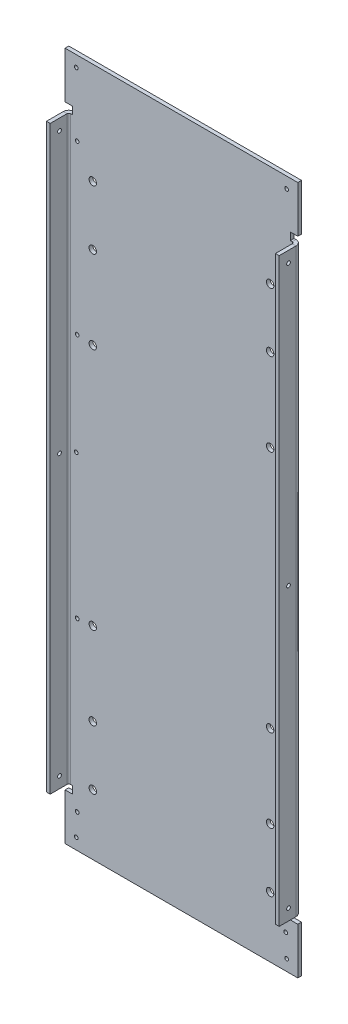
SolidWorks part; units mm, degrees
note: The reader was unsure of these and kept them because the rebuilt part matched: flange length of "Edge-Flange1".
ref_plane "Front Plane" through (0, 0, 0) normal (1, 0, 0) x (0, 1, 0)
ref_plane "Top Plane" through (0, 0, 0) normal (0, 0, 1) x (0, 1, 0)
ref_plane "Right Plane" through (0, 0, 0) normal (0, 1, 0) x (-1, 0, 0)
sketch "Sketch1" plane through (0, 0, 0) normal (0, 0, 1) x (0, 1, 0)
  line L0 (-76.28, 47.625) -> (-76.28, -47.625) construction
  line L1 (185, 62.5) -> (160, 62.5)
  line L2 (185, 62.5) -> (185, -62.5)
  line L3 (185, -62.5) -> (160, -62.5)
  line L4 (-185, 62.5) -> (-185, -62.5)
  line L5 (185, 62.5) -> (-185, -62.5) construction
  line L6 (185, -62.5) -> (-185, 62.5) construction
  line L7 (-11, 62.5) -> (-11, -62.5) construction
  line L8 (-182, 50.8) -> (-35, 50.8) construction
  line L9 (-182, 50.8) -> (-182, -50.8) construction
  line L10 (-182, -50.8) -> (-35, -50.8) construction
  line L11 (-35, 50.8) -> (-35, -50.8) construction
  line L12 (160, -50.8) -> (13, -50.8) construction
  line L13 (13, 50.8) -> (13, -50.8) construction
  line L14 (160, 50.8) -> (13, 50.8) construction
  line L15 (160, 50.8) -> (160, -50.8) construction
  line L16 (155, 62.5) -> (155, -62.5) construction
  line L17 (-160, 62.5) -> (-160, 58.5)
  line L18 (-160, 58.5) -> (-156, 58.5)
  line L19 (-156, 58.5) -> (-156, 62.5)
  line L20 (156, 62.5) -> (156, 58.5)
  line L21 (156, 58.5) -> (160, 58.5)
  line L22 (160, 58.5) -> (160, 62.5)
  line L23 (-185, 0) -> (185, 0) construction
  line L24 (160, -58.5) -> (160, -62.5)
  line L25 (156, -58.5) -> (160, -58.5)
  line L26 (156, -62.5) -> (156, -58.5)
  line L27 (-156, -58.5) -> (-156, -62.5)
  line L28 (-160, -58.5) -> (-156, -58.5)
  line L29 (-160, -62.5) -> (-160, -58.5)
  line L30 (156, 62.5) -> (-156, 62.5)
  line L31 (-160, 62.5) -> (-185, 62.5)
  line L32 (156, -62.5) -> (-156, -62.5)
  line L33 (-160, -62.5) -> (-185, -62.5)
  circle A0 centre (-152.48, 47.625) radius 2
  circle A1 centre (-120.73, 47.625) radius 2
  circle A2 centre (-76.28, 47.625) radius 2
  circle A3 centre (-152.48, -47.625) radius 2
  circle A4 centre (-120.73, -47.625) radius 2
  circle A5 centre (-76.28, -47.625) radius 2
  circle A6 centre (54.28, 47.625) radius 2
  circle A7 centre (98.73, 47.625) radius 2
  circle A8 centre (130.48, 47.625) radius 2
  circle A9 centre (130.48, -47.625) radius 2
  circle A10 centre (98.73, -47.625) radius 2
  circle A11 centre (54.28, -47.625) radius 2
  circle A12 centre (-179, 56.5) radius 1
  circle A13 centre (-179, -56.5) radius 1
  circle A14 centre (179, -56.5) radius 1
  circle A15 centre (179, 56.5) radius 1
  circle A16 centre (0, 56.5) radius 1
  circle A17 centre (0, -56.5) radius 1
  circle A18 centre (-167, 56) radius 1
  circle A19 centre (-77, 56) radius 1
  circle A20 centre (-167, -56) radius 1
  circle A21 centre (-77, -56) radius 1
  circle A22 centre (55, -56) radius 1
  circle A23 centre (145, -56) radius 1
  circle A24 centre (55, 56) radius 1
  circle A25 centre (145, 56) radius 1
  point P0 (0, 0)
  point P18 (-76.28, 0)
  point P19 (-35, 0)
  dimension "D3" = 4
  dimension "D18" = 2
  dimension "D23" = 2
  dimension "D1" = 125
  dimension "D2" = 370
  dimension "D4" = 76.2
  dimension "D5" = 44.45
  dimension "D6" = 95.25
  dimension "D7" = 41.28
  dimension "D8" = 147
  dimension "D9" = 3
  dimension "D10" = 101.6
  dimension "D11" = 174
  dimension "D12" = 30
  dimension "D13" = 160
  dimension "D14" = 160
  dimension "D15" = 4
  dimension "D16" = 4
  dimension "D17" = 4
  dimension "D19" = 6
  dimension "D20" = 6
  dimension "D21" = 6
  dimension "D22" = 6
  dimension "D24" = 56
  dimension "D25" = 56
  dimension "D26" = 15
  dimension "D27" = 90
base flange "Base-Flange1" sketch "Sketch1" thickness 2 reverse thickness direction no parameters "D1"=0.9652
edge flange "Edge-Flange1" sketch "Sketch11" flange profiles "Sketch11", "Sketch12" flange angle 90 flange length 12 flange position material inside bend radius 0.9652 thickness 2 relief rectangular parameters "D1"=0.7366, "D6"=10, "D8"=1
sketch "Sketch11" plane through (-62.5, 0, 0) normal (-1, 0, 0) x (0, -1, 0)
  line L0 (-156, 0) -> (156, 0) construction
  line L1 (-156, 0) -> (156, 0)
  line L2 (-156, 0) -> (-156, 10)
  line L3 (-156, 10) -> (156, 10)
  line L4 (156, 10) -> (156, 0)
sketch "Sketch12" plane through (62.5, 0, 0) normal (1, 0, 0) x (0, 1, 0)
  line L0 (-156, 0) -> (156, 0) construction
  line L1 (-156, 0) -> (156, 0)
  line L2 (-156, 0) -> (-156, 10)
  line L3 (-156, 10) -> (156, 10)
  line L4 (156, 10) -> (156, 0)
bend "EdgeBend1" bend radius 0.9652 bend angle 90 parameters "D5"=1
bend "EdgeBend2" bend radius 0.9652 bend angle 90 parameters "D5"=2
sketch "Sketch13" plane through (62.5, 0, 0) normal (1, 0, 0) x (0, 1, 0)
  line L0 (156, -2) -> (-156, -2) construction
  circle A0 centre (0, 5) radius 1
  circle A1 centre (150, 5) radius 1
  circle A2 centre (-150, 5) radius 1
  dimension "D1" = 2
  dimension "D2" = 7
  dimension "D3" = 150
  dimension "D4" = 150
extrude "Cut-Extrude1" cut sketch "Sketch13" against normal through all normal cut yes
sketch "Bend-Lines1" [suppressed] plane through (0, 0, 0) normal (0, 1, 0) x (-1, 0, 0)
sketch "Bounding-Box1" [suppressed] plane through (0, 0, 0) normal (0, 1, 0) x (-1, 0, 0)
sheet metal parameters "Sheet-Metal1" thickness 2 parameters "D1"=0.7366
flat pattern "Flat-Pattern1" [suppressed]
sketch "Bend-Lines2" plane through (0, 0, 0) normal (0, 1, 0) x (-1, 0, 0)
sketch "Bounding-Box2" [suppressed] plane through (0, 0, 0) normal (0, 1, 0) x (-1, 0, 0)
sheet metal parameters "Sheet-Metal2" thickness 2 parameters "D1"=0.7366
flat pattern "Flat-Pattern1" [suppressed]
sketch "Bend-Lines2" plane through (0, 0, 0) normal (0, 1, 0) x (-1, 0, 0)
sketch "Bounding-Box2" [suppressed] plane through (0, 0, 0) normal (0, 1, 0) x (-1, 0, 0)
bend of the flat pattern "Flatten-<EdgeBend1>1"
bend of the flat pattern "Flatten-<EdgeBend2>1"
sheet metal parameters "Sheet-Metal3" thickness 2 parameters "D1"=0.7366
flat pattern "Flat-Pattern1"
sketch "Bend-Lines2" plane through (0, 0, 0) normal (0, 0, 1) x (0, -1, 0)
  line L0 (156, 61.0783) -> (-156, 61.0783) construction
  line L1 (-156, -61.0783) -> (156, -61.0783) construction
  line L2 (156, 61.0783) -> (-156, 61.0783) construction
  line L3 (-156, -61.0783) -> (156, -61.0783) construction
sketch3d "Bounding-Box2" [suppressed]
  line L0 (-185, 71.6565, 0) -> (185, 71.6565, 0) construction
  line L1 (-185, -71.6565, 0) -> (185, -71.6565, 0) construction
  line L2 (-185, 71.6565, 0) -> (-185, -71.6565, 0) construction
  line L3 (185, 71.6565, 0) -> (185, -71.6565, 0) construction
bend of the flat pattern "Flatten-<EdgeBend1>1"
bend of the flat pattern "Flatten-<EdgeBend2>1"
